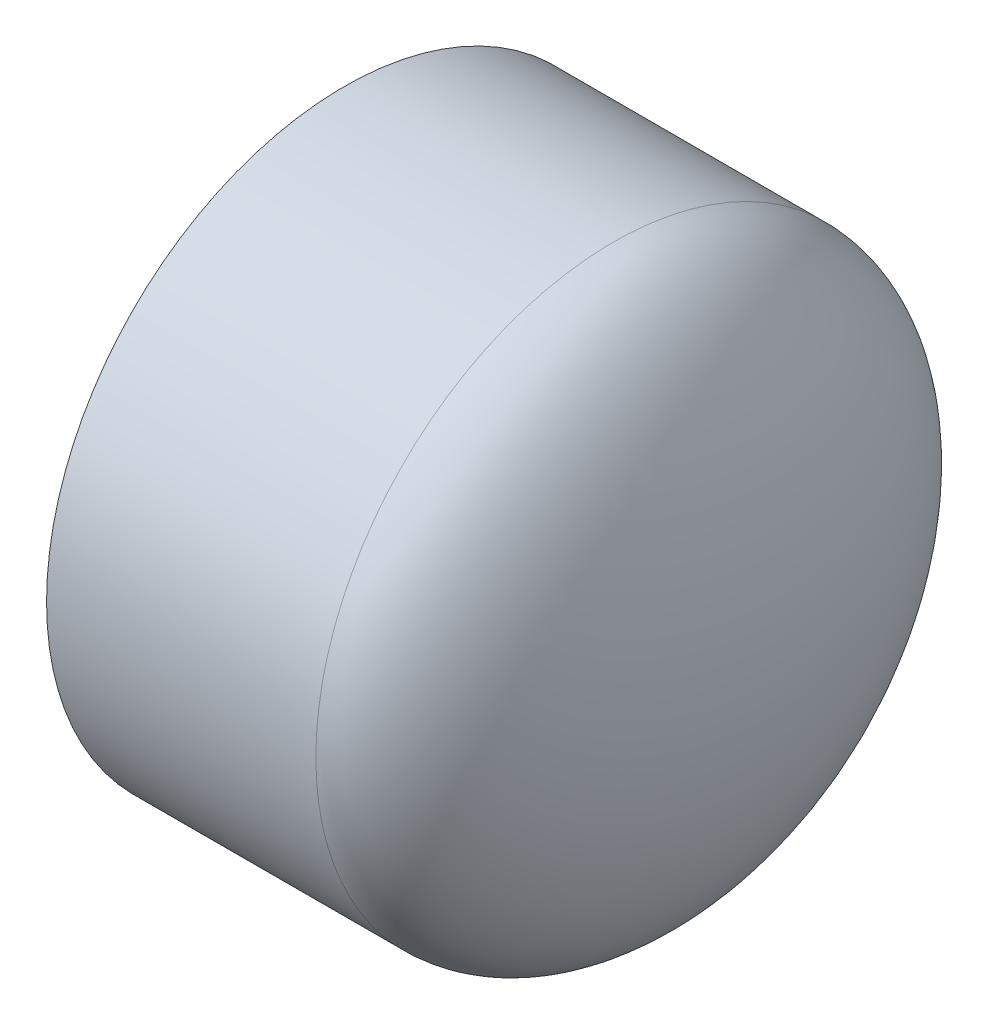
SolidWorks part; units mm, degrees
ref_plane "Front Plane" through (0, 0, 0) normal (0, 0, 1) x (1, 0, 0)
ref_plane "Top Plane" through (0, 0, 0) normal (0, 1, 0) x (1, 0, 0)
ref_plane "Right Plane" through (0, 0, 0) normal (1, 0, 0) x (0, 0, -1)
sketch "Sketch0" plane through (0, 0, 0) normal (0, 0, 1) x (1, 0, 0)
  line L0 (-74.93, 0) -> (0, 0) construction
  line L2 (-25.4, 0) -> (0, 0) construction
  line L4 (-74.93, 54.737) -> (-74.93, -54.737) construction
  line L5 (-25.4, 44.3484) -> (-74.93, 44.6532) construction
  line L6 (-25.4, 44.3484) -> (-25.4, -44.3484) construction
  line L7 (-25.4, -44.3484) -> (-74.93, -44.6532) construction
  line L8 (-74.93, 44.6532) -> (-74.93, -44.6532) construction
  line L14 (-25.4, 36.83) -> (-25.4, -36.83) construction
  dimension "M" = 109.474
  dimension "OD A" = 89.3064
  dimension "OD B" = 88.6968
  dimension "ID" = 73.66
  dimension "W" = 74.93
  dimension "C" = 49.53
sketch "Sketch1" plane through (0, 0, 0) normal (0, 0, 1) x (1, 0, 0)
  line L0 (-74.93, 0) -> (0, 0) construction
  line L1 (-74.93, 0) -> (0, 0) construction
  line L2 (-25.4, 0) -> (0, 0) construction
  line L3 (-74.93, -54.737) -> (-25.4, -54.737)
  line L4 (-74.93, -54.737) -> (-74.93, -44.6532)
  line L5 (-74.93, -44.6532) -> (-25.4, -44.3484)
  line L6 (-25.4, 0) -> (-25.4, -44.3484) construction
  line L7 (-25.4, -44.3484) -> (-25.4, -54.737) construction
  line L8 (-10.3886, 0) -> (0, 0)
  ellipse E0 centre (-25.4, 0) end of major axis (-25.4, 54.737) minor radius 25.4 (-25.4, -54.737) -> (0, 0) ccw
  ellipse E1 centre (-25.4, 0) end of major axis (-25.4, -44.3484) minor radius 15.0114 (-25.4, -44.3484) -> (-10.3886, 0) ccw
revolve "Revolve1" add sketch "Sketch1" angle 360 about L1
other "CPoint1" parameters "Diameter"=76.2, "StubLength"=76.2
ref_axis "Axis1" through (-35.4, 0, 0) along (1, 0, 0)
other "RPoint1"
